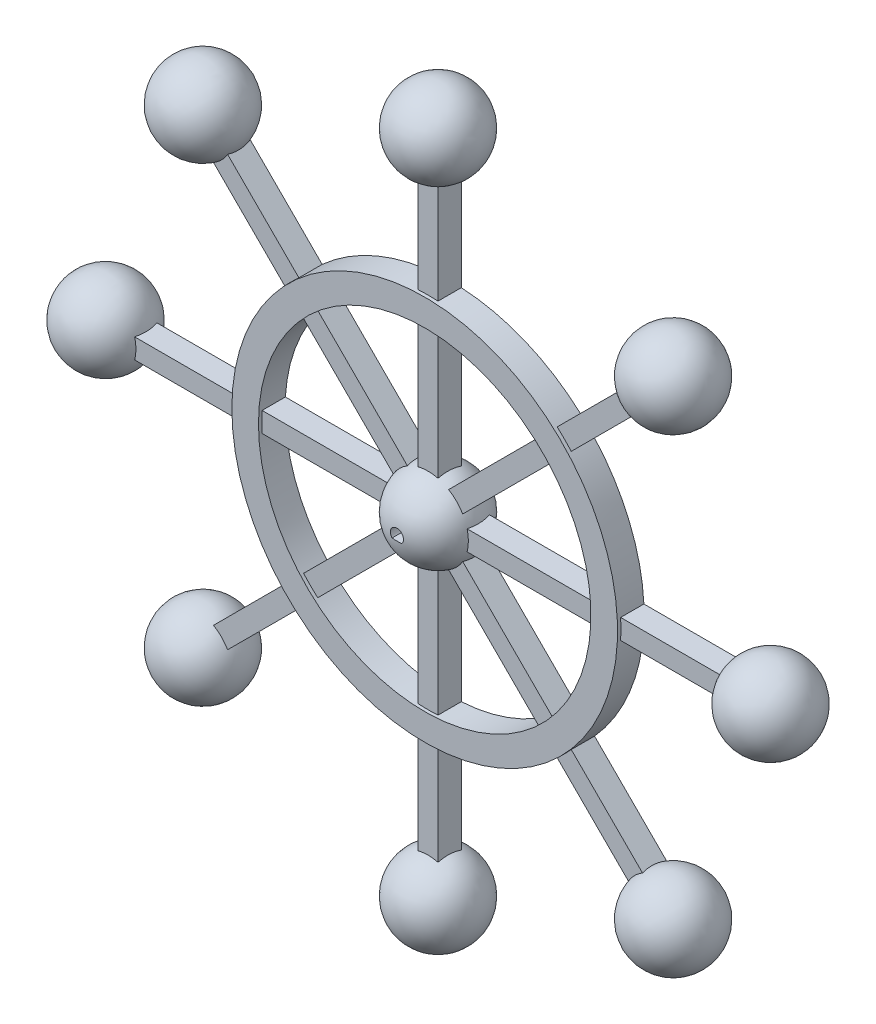
SolidWorks part; units mm, degrees
material "Plain Carbon Steel"
ref_plane "Front Plane" through (0, 0, 0) normal (0, 0, 1) x (1, 0, 0)
ref_plane "Top Plane" through (0, 0, 0) normal (0, 1, 0) x (1, 0, 0)
ref_plane "Right Plane" through (0, 0, 0) normal (1, 0, 0) x (0, 0, -1)
sketch "Sketch1" plane through (0, 0, 0) normal (0, 0, 1) x (1, 0, 0)
  line L0 (0, 15.875) -> (0, -15.875)
  arc A0 (0, -15.875) -> (0, 15.875) centre (0, 0) ccw
  dimension "D1" = 31.75
revolve "Revolve1" add sketch "Sketch1" angle 360 about L0
sketch "Sketch2" plane through (0, 0, 0) normal (0, 0, 1) x (1, 0, 0)
  line L0 (0, 0) -> (127, 0) construction
  line L1 (0, -3.81) -> (127, -3.81)
  line L2 (0, 3.81) -> (127, 3.81)
  line L3 (127, 3.81) -> (127, -3.81)
  line L4 (0, 3.81) -> (0, -3.81)
  dimension "D1" = 127
  dimension "D2" = 3.81
  dimension "D3" = 3.81
extrude "Boss-Extrude1" add sketch "Sketch2" along normal blind 3.81 and the other way blind 5.08
sketch "Sketch3" plane through (0, 0, 0) normal (0, 1, 0) x (1, 0, 0)
  line L0 (0, 0) -> (0, 8.1282) construction
pattern_circular "CirPattern1" count 8 over 360 about axis through (0, 0, 0) along (0, 0, -1) of "Boss-Extrude1" reverse direction yes
sketch "Sketch5" plane through (0, 0, -5.08) normal (0, 0, -1) x (-1, 0, 0)
  circle A0 centre (0, 0) radius 63.5
  circle A1 centre (0, 0) radius 73.66
  dimension "D1" = 127
  dimension "D2" = 10.16
extrude "Boss-Extrude2" add sketch "Sketch5" against normal blind 10.16
sketch "Sketch6" plane through (0, 0, -5.08) normal (0, 0, -1) x (-1, 0, 0)
  line L0 (-1.8555, -1.6783) -> (1.8555, -1.6783)
  arc A0 (1.8555, -1.6783) -> (-1.8555, -1.6783) centre (0, 0) ccw
  dimension "D1" = 5.0038
  dimension "D2" = 3.711
extrude "Cut-Extrude1" cut sketch "Sketch6" against normal through all and the other way through all
sketch "Sketch7" plane through (0, 0, 0) normal (0, 0, 1) x (1, 0, 0)
  line L0 (3.81, 127) -> (-3.81, 127) construction
  line L1 (0, 111.125) -> (0, 142.875)
  arc A0 (0, 111.125) -> (0, 142.875) centre (0, 127) ccw
  dimension "D1" = 31.75
revolve "Revolve2" add sketch "Sketch7" angle 360 about L1
pattern_circular "CirPattern2" count 8 over 360 about axis through (0, 0, 0) along (0, 0, -1) of "Revolve2"
